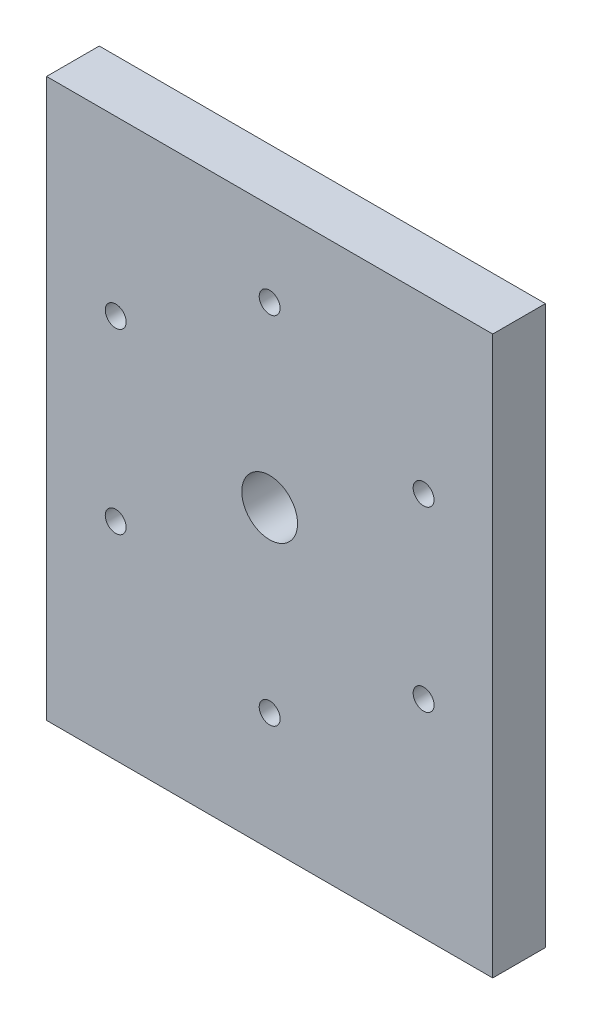
SolidWorks part; units mm, degrees
ref_plane "Front Plane" through (0, 0, 0) normal (0, 0, 1) x (1, 0, 0)
ref_plane "Top Plane" through (0, 0, 0) normal (0, 1, 0) x (1, 0, 0)
ref_plane "Right Plane" through (0, 0, 0) normal (1, 0, 0) x (0, 0, -1)
sketch "Sketch1" plane through (0, 0, 0) normal (0, 0, 1) x (1, 0, 0)
  line L0 (34.1802, 50.5429) -> (34.1802, 53.0508) construction
  line L1 (-50.8, 127) -> (50.8, 127)
  line L2 (-50.8, 127) -> (-50.8, 0)
  line L3 (-50.8, 0) -> (50.8, 0)
  line L4 (50.8, 127) -> (50.8, 0)
  circle A0 centre (0, 67.375) radius 6.35
  circle A7 centre (0, 67.375) radius 38.1 construction
  point P6 (0, 0)
  point P22 (0, 0)
  point P23 (0, 0)
  dimension "D1" = 127
  dimension "D3" = 12.7
  dimension "D12" = 76.2
  dimension "D2" = 101.6
  dimension "D5" = 67.375
extrude "Boss-Extrude1" add sketch "Sketch1" along normal blind 12
sketch "Sketch2" plane through (0, 0, 0) normal (0, 0, -1) x (-1, 0, 0)
  circle A0 centre (0, 107.8562) radius 2.3812
  circle A1 centre (0, 67.375) radius 38.1 construction
  point P5 (0, 0)
  dimension "D1" = 4.7625
extrude "Cut-Extrude1" cut sketch "Sketch2" against normal through all
pattern_circular "CirPattern1" count 6 every 60 about axis through (0, 67.375, 12) along (0, 0, -1) of "Cut-Extrude1"
